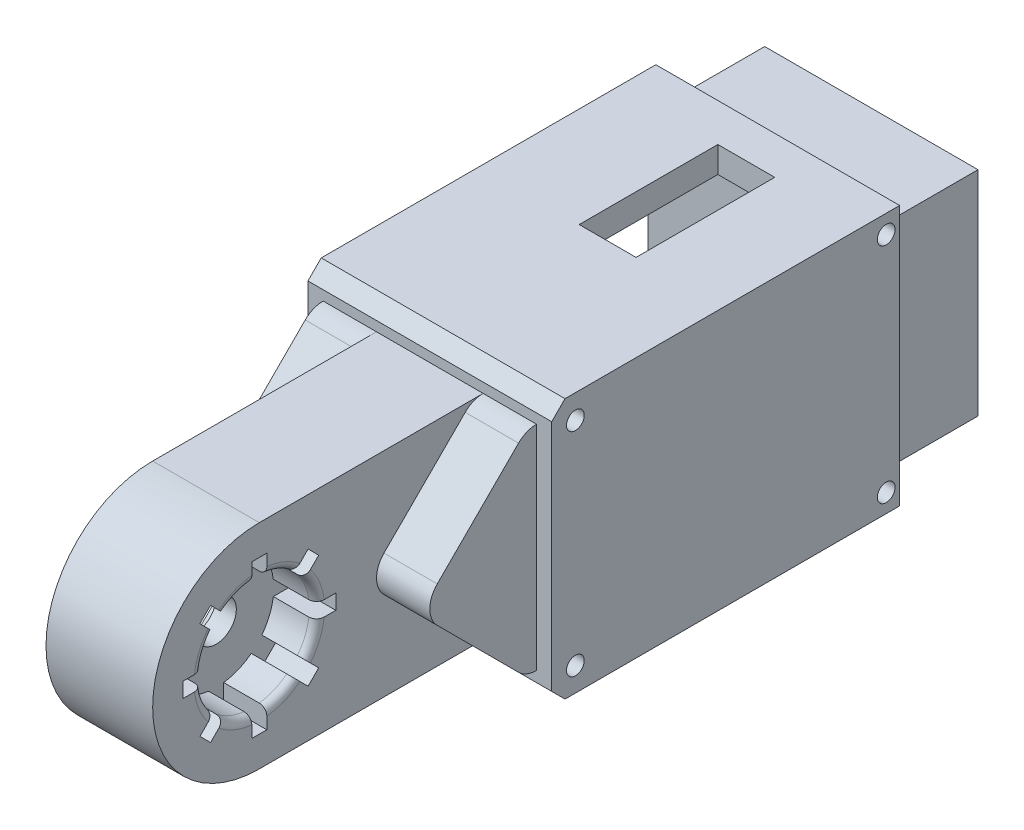
SolidWorks part; units mm, degrees
ref_plane "Front Plane" through (0, 0, 0) normal (0, 0, 1) x (1, 0, 0)
ref_plane "Top Plane" through (0, 0, 0) normal (0, 1, 0) x (1, 0, 0)
ref_plane "Right Plane" through (0, 0, 0) normal (1, 0, 0) x (0, 0, -1)
sketch "Sketch2" plane through (0, 0, 0) normal (0, 0, 1) x (1, 0, 0)
  line L1 (-21, 21) -> (21, 21)
  line L2 (-21, 21) -> (-21, -21)
  line L3 (-21, -21) -> (21, -21)
  line L4 (21, 21) -> (21, -21)
  line L5 (-21, 21) -> (21, -21) construction
  line L6 (-21, -21) -> (21, 21) construction
  point P0 (0, 0)
  dimension "D1" = 42
  dimension "D2" = 42
extrude "Boss-Extrude1" add sketch "Sketch2" along normal blind 89
ref_plane "Plane1" through (0, 0, 89) normal (0, 0, 1) x (1, 0, 0)
sketch "Sketch3" plane through (0, 0, 89) normal (0, 0, 1) x (1, 0, 0)
  line L0 (21, 21) -> (-21, 21) construction
  line L1 (10.5, -21) -> (-10.5, -21)
  line L2 (10.5, -21) -> (10.5, 21)
  line L3 (10.5, 21) -> (-10.5, 21)
  line L4 (-10.5, -21) -> (-10.5, 21)
  line L5 (10.5, -21) -> (-10.5, 21) construction
  line L6 (10.5, 21) -> (-10.5, -21) construction
  point P0 (0, 0)
  dimension "D1" = 21
ref_plane "Plane4" through (0, 0, 0) normal (0, 0, -1) x (-1, 0, 0)
extrude "Boss-Extrude2" add sketch "Sketch3" along normal blind 42
ref_plane "Plane5" through (-10.5, 0, 0) normal (-1, 0, 0) x (0, 0, 1)
sketch "Sketch8" plane through (-10.5, 0, 0) normal (-1, 0, 0) x (0, 0, 1)
  line L0 (131, 21) -> (131, -21) construction
  line L1 (131, 21) -> (131, -21)
  arc A0 (131, 21) -> (131, -21) centre (131, 0) cw
  dimension "D1" = 21
extrude "Boss-Extrude3" add sketch "Sketch8" against normal blind 21
ref_plane "Plane6" through (-10.5, 0, 0) normal (-1, 0, 0) x (0, 0, 1)
sketch "Sketch9" plane through (-10.5, 0, 0) normal (-1, 0, 0) x (0, 0, 1)
  line L0 (89, 21) -> (89, -21) construction
  line L1 (131, 21) -> (131, -21)
  circle A0 centre (131, 0) radius 11.35
  dimension "D1" = 42
  dimension "D2" = 22.7
extrude "Cut-Extrude2" cut sketch "Sketch9" against normal blind 8.5 contours A0
ref_plane "Plane7" through (10.5, 0, 0) normal (1, 0, 0) x (0, 0, -1)
sketch "Sketch11" plane through (10.5, 0, 0) normal (1, 0, 0) x (0, 0, -1)
  line L0 (-131, 21) -> (-131, -21)
  circle A0 centre (-131, 0) radius 11.35
  dimension "D1" = 22.7
extrude "Cut-Extrude3" cut sketch "Sketch11" against normal blind 8.5 contours A0
ref_plane "Plane8" through (-2, 0, 0) normal (-1, 0, 0) x (0, 0, 1)
sketch "Sketch12" plane through (-2, 0, 0) normal (-1, 0, 0) x (0, 0, 1)
  circle A0 centre (131, 0) radius 3.975
  dimension "D1" = 7.95
extrude "Cut-Extrude4" cut sketch "Sketch12" against normal through all
ref_plane "Plane10" through (-2, 0, 0) normal (-1, 0, 0) x (0, 0, 1)
ref_plane "Plane11" through (-10.5, 0, 0) normal (-1, 0, 0) x (0, 0, 1)
sketch "Sketch20" plane through (-10.5, 0, 0) normal (-1, 0, 0) x (0, 0, 1)
  line L0 (131, 0) -> (110, 0)
  line L1 (110, 0) -> (110, 21)
  line L2 (110, 0) -> (110, -21)
  line L4 (110, 21) -> (89, 21)
  line L6 (110, -21) -> (89, -21)
  line L7 (89, 21) -> (110, 0)
  line L8 (89, -21) -> (110, 0)
  line L9 (89, 21) -> (89, -21)
  circle A0 centre (131, 0) radius 11.35
  dimension "D1" = 21
extrude "Boss-Extrude4" add sketch "Sketch20" along normal blind 10.5 and the other way blind 31.5 contours L7 L9 L8 region at (-10.5, 0, 96)
fillet "Fillet1" radius 5 1 edges at (15.75, 0, 110)
fillet "Fillet2" radius 5 1 edges at (-15.75, 0, 110)
fillet "Fillet3" radius 5 1 edges at (-15.75, -21, 89)
fillet "Fillet4" radius 5 1 edges at (-15.75, 21, 89)
fillet "Fillet5" radius 5 1 edges at (15.75, -21, 89)
fillet "Fillet6" radius 5 1 edges at (15.75, 21, 89)
fillet "Fillet7" radius 1.5 1 edges at (-10.5, 0, 142.35)
fillet "Fillet8" radius 1.5 1 edges at (10.5, 0, 119.65)
sketch "Sketch21" plane through (-10.5, 0, 0) normal (-1, 0, 0) x (0, 0, 1)
  line L1 (129.5207, 10.6415) -> (132.4793, 10.6415)
  line L2 (129.5207, 10.6415) -> (129.5207, 15.0585)
  line L3 (129.5207, 15.0585) -> (132.4793, 15.0585)
  line L4 (132.4793, 10.6415) -> (132.4793, 15.0585)
  line L5 (129.5207, 10.6415) -> (132.4793, 15.0585) construction
  line L6 (129.5207, 15.0585) -> (132.4793, 10.6415) construction
  circle A0 centre (131, 0) radius 12.85 construction
  point P0 (131, 12.85)
  dimension "D1" = 4.417
extrude "Cut-Extrude5" cut sketch "Sketch21" against normal blind 8.5
pattern_circular "CirPattern2" count 8 over 360 about axis through (-9, 0, 131) along (-1, 0, 0) of "Cut-Extrude5"
ref_plane "Plane12" through (0, 21, 0) normal (0, 1, 0) x (1, 0, 0)
ref_plane "Plane13" through (10.5, 0, 0) normal (1, 0, 0) x (0, 0, -1)
ref_plane "Plane14" through (0, 0, 0) normal (1, 0, 0) x (0, 0, -1)
mirror "Mirror1" about plane through (0, 0, 0) normal (1, 0, 0) of "CirPattern2"
ref_plane "Plane15" through (21, 0, 0) normal (1, 0, 0) x (0, 0, -1)
sketch "Sketch24" plane through (21, 0, 0) normal (1, 0, 0) x (0, 0, -1)
  line L1 (-86.9289, 21) -> (0, 21)
  line L2 (-86.9289, 21) -> (-86.9289, 25.5452)
  line L3 (-86.9289, 25.5452) -> (0, 25.5452)
  line L4 (0, 21) -> (0, 25.5452)
  line L5 (-86.9289, -21) -> (0, -21)
  line L6 (-86.9289, -21) -> (-86.9289, -25.6891)
  line L7 (-86.9289, -25.6891) -> (0, -25.6891)
  line L8 (0, -21) -> (0, -25.6891)
extrude "Boss-Extrude6" add sketch "Sketch24" against normal blind 42
sketch "Sketch25" plane through (21, 0, 0) normal (1, 0, 0) x (0, 0, -1)
  line L0 (-18.4289, -25.6891) -> (-18.4289, 25.5452)
  line L1 (-86.9289, 25.5452) -> (-18.4289, 25.5452)
  line L2 (-86.9289, 25.5452) -> (-86.9289, -25.6891)
  line L3 (-86.9289, -25.6891) -> (-18.4289, -25.6891)
  dimension "D1" = 68.5
extrude "Boss-Extrude7" add sketch "Sketch25" along normal blind 3
ref_plane "Plane18" through (0, 0, 0) normal (0, 0, -1) x (-1, 0, 0)
ref_plane "Plane19" through (-21, 0, 0) normal (-1, 0, 0) x (0, 0, 1)
sketch "Sketch28" plane through (-21, 0, 0) normal (-1, 0, 0) x (0, 0, 1)
  line L0 (86.9289, -25.6891) -> (0, -25.6891) construction
  line L1 (86.9289, 25.5452) -> (18.4289, 25.5452)
  line L2 (86.9289, 25.5452) -> (86.9289, -25.6891)
  line L3 (86.9289, -25.6891) -> (18.4289, -25.6891)
  line L4 (18.4289, 25.5452) -> (18.4289, -25.6891)
  dimension "D1" = 68.5
extrude "Boss-Extrude8" add sketch "Sketch28" along normal blind 3
ref_plane "Plane20" through (-24, 0, 0) normal (-1, 0, 0) x (0, 0, 1)
sketch "Sketch30" plane through (-24, 0, 0) normal (-1, 0, 0) x (0, 0, 1)
  line L1 (81.9289, 20.4302) -> (19.9289, 20.4302)
  line L2 (81.9289, 20.4302) -> (81.9289, -20.5741)
  line L3 (81.9289, -20.5741) -> (19.9289, -20.5741)
  line L4 (19.9289, 20.4302) -> (19.9289, -20.5741)
  line L5 (81.9289, 20.4302) -> (19.9289, -20.5741) construction
  line L6 (81.9289, -20.5741) -> (19.9289, 20.4302) construction
  line L8 (86.9289, 25.5452) -> (18.4289, 25.5452) construction
  line L9 (18.4289, -25.6891) -> (86.9289, -25.6891) construction
  line L10 (86.9289, -21) -> (86.9289, 21) construction
  point P0 (50.9289, -0.0719)
  dimension "D1" = 5.115
  dimension "D2" = 5.115
  dimension "D3" = 62
  dimension "D4" = 5
extrude "Cut-Extrude6" cut sketch "Sketch30" against normal blind 45
ref_plane "Plane21" through (21, 0, 0) normal (1, 0, 0) x (0, 0, -1)
sketch "Sketch31" plane through (21, 0, 0) normal (1, 0, 0) x (0, 0, -1)
  line L0 (0, -25.6891) -> (0, 25.5452) construction
  line L1 (-18.4289, -25.6891) -> (0, -25.6891)
  line L2 (-18.4289, -25.6891) -> (-18.4289, -21.0741)
  line L3 (-18.4289, -21.0741) -> (0, -21.0741)
  line L4 (0, -25.6891) -> (0, -21.0741)
  line L6 (-18.4289, 25.5452) -> (0, 25.5452)
  line L7 (-18.4289, 25.5452) -> (-18.4289, 20.9302)
  line L8 (-18.4289, 20.9302) -> (0, 20.9302)
  line L9 (0, 25.5452) -> (0, 20.9302)
  dimension "D1" = 4.615
  dimension "D2" = 4.615
extrude "Cut-Extrude7" cut sketch "Sketch31" against normal through all
chamfer "Chamfer1" distance 1.5 angle 45 4 edges at (0, 20.9302, 18.4289) (21, -0.0719, 18.4289) (0, -21.0741, 18.4289) (-21, -0.0719, 18.4289)
ref_plane "Plane22" through (0, 0, 0) normal (0, 0, -1) x (-1, 0, 0)
sketch "Sketch32" plane through (0, 0, 0) normal (0, 0, -1) x (-1, 0, 0)
  line L1 (15, 15) -> (-15, 15)
  line L2 (15, 15) -> (15, -15)
  line L3 (15, -15) -> (-15, -15)
  line L4 (-15, 15) -> (-15, -15)
  line L5 (15, 15) -> (-15, -15) construction
  line L6 (15, -15) -> (-15, 15) construction
  point P0 (0, 0)
  dimension "D1" = 30
  dimension "D2" = 30
extrude "Cut-Extrude8" cut sketch "Sketch32" against normal blind 16.8
ref_plane "Plane23" through (0, 0, 19.9289) normal (0, 0, 1) x (1, 0, 0)
sketch "Sketch33" plane through (0, 0, 19.9289) normal (0, 0, 1) x (1, 0, 0)
  circle A0 centre (0, 0) radius 5
  dimension "D1" = 10
extrude "Cut-Extrude9" cut sketch "Sketch33" against normal blind 16.8
ref_plane "Plane24" through (-21, 0, 0) normal (-1, 0, 0) x (0, 0, 1)
sketch "Sketch34" plane through (-24, 0, 0) normal (-1, 0, 0) x (0, 0, 1)
  line L0 (86.9289, -0.0719) -> (103.6427, -0.0719) construction
  line L2 (88.3304, -21.6696) -> (88.3304, -28.2221)
  line L3 (88.3304, -28.2221) -> (81.7779, -28.2221)
  line L4 (81.7779, -28.2221) -> (88.3304, -21.6696)
  line L5 (86.9289, -25.6891) -> (86.9289, 25.5452) construction
  line L6 (88.3304, 28.0782) -> (81.7779, 28.0782)
  line L7 (88.3304, 21.5257) -> (88.3304, 28.0782)
  line L8 (81.7779, 28.0782) -> (88.3304, 21.5257)
extrude "Cut-Extrude10" cut sketch "Sketch34" against normal through all
chamfer "Chamfer2" distance 6 angle 45 1 edges at (-1.5, 20.4302, 81.9289)
chamfer "Chamfer3" distance 6 angle 45 1 edges at (-1.5, -20.5741, 81.9289)
chamfer "Chamfer4" distance 6 angle 45 1 edges at (-1.5, 20.4302, 19.9289)
chamfer "Chamfer5" distance 6 angle 45 1 edges at (-1.5, -20.5741, 19.9289)
sketch "Sketch35" plane through (-24, 0, 0) normal (-1, 0, 0) x (0, 0, 1)
  line L0 (78.9289, -17.5741) -> (85.6199, -24.3801) construction
  line L1 (82.2744, 20.8332) -> (85.6199, 24.2362) construction
  line L2 (81.9289, -14.5741) -> (75.9289, -20.5741) construction
  line L3 (84.3109, -25.6891) -> (86.9289, -23.0711) construction
  line L4 (78.9289, 17.4302) -> (85.6199, 24.2362) construction
  line L5 (75.9289, 20.4302) -> (81.9289, 14.4302) construction
  line L6 (86.9289, 22.9272) -> (84.3109, 25.5452) construction
  line L7 (18.4289, 25.5452) -> (21.0741, 21.9048) construction
  line L9 (18.4289, -25.6891) -> (21.074, -22.0485) construction
  line L10 (18.4289, 25.5452) -> (18.4289, -25.6891) construction
  circle A0 centre (21.0741, 21.9048) radius 1.75
  circle A1 centre (82.2744, 20.8332) radius 1.75
  circle A2 centre (82.2744, -20.9771) radius 1.75
  circle A3 centre (21.074, -22.0485) radius 1.75
  dimension "D5" = 3.5
  dimension "D1" = 36.003
  dimension "D2" = 36
  dimension "D3" = 4.5
  dimension "D4" = 4.5
extrude "Cut-Extrude11" cut sketch "Sketch35" against normal through all
ref_plane "Plane26" through (0, -25.6891, 0) normal (0, -1, 0) x (-1, 0, 0)
sketch "Sketch38" plane through (0, -25.6891, 0) normal (0, -1, 0) x (-1, 0, 0)
  line L0 (-24, -18.4289) -> (24, -18.4289) construction
  line L1 (4.2922, -53.2289) -> (-6.9078, -53.2289)
  line L2 (4.2922, -53.2289) -> (4.2922, -25.9289)
  line L3 (4.2922, -25.9289) -> (-6.9078, -25.9289)
  line L4 (-6.9078, -53.2289) -> (-6.9078, -25.9289)
  dimension "D1" = 7.5
  dimension "D2" = 27.3
  dimension "D3" = 11.2
extrude "Cut-Extrude12" cut sketch "Sketch38" against normal through all
